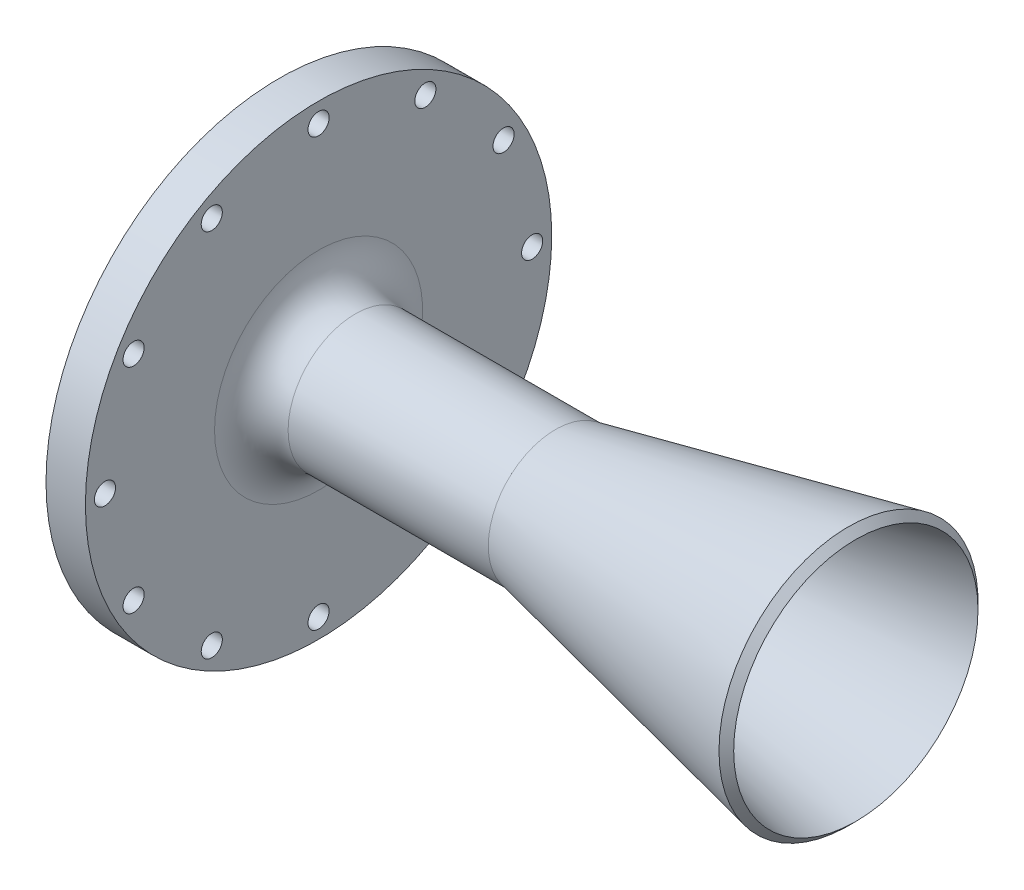
SolidWorks part; units mm, degrees
material "Stainless Steel (ferritic)"
ref_plane "Front Plane" through (0, 0, 0) normal (0, 0, 1) x (1, 0, 0)
ref_plane "Top Plane" through (0, 0, 0) normal (0, 1, 0) x (1, 0, 0)
ref_plane "Right Plane" through (0, 0, 0) normal (1, 0, 0) x (0, 0, -1)
sketch "Sketch2" plane through (0, 0, 0) normal (0, 0, 1) x (1, 0, 0)
  line L0 (0, 0) -> (165.0115, 0) construction
  line L1 (0, 20.5835) -> (0, 56.3562)
  line L2 (0, 56.3562) -> (9.525, 56.3562)
  line L3 (9.525, 56.3562) -> (9.525, 16.256)
  line L11 (66.8065, 16.256) -> (139.7, 31.75)
  line L17 (139.7, 31.75) -> (139.7, 29.5925)
  line L18 (60.325, 12.7208) -> (60.325, 14.351)
  line L19 (60.325, 14.351) -> (10.795, 14.351)
  line L20 (0, 20.5835) -> (10.795, 14.351)
  line L21 (60.325, 12.7208) -> (139.7, 29.5925)
  line L22 (9.525, 16.256) -> (66.8065, 16.256)
  dimension "D2" = 9.525
  dimension "D3" = 1.905
  dimension "D4" = 10.795
  dimension "D5" = 14.351
  dimension "D6" = 31.75
  dimension "D7" = 12
  dimension "D8" = 139.7
  dimension "D9" = 1.6302
  dimension "D10" = 30
  dimension "D11" = 56.3562
  dimension "D12" = 49.53
revolve "Main Structure" add sketch "Sketch2" angle 360 about L0
sketch "Sketch4" plane through (0, 0, 0) normal (-1, 0, 0) x (0, 0, 1)
  circle A0 centre (0, 0) radius 51.6255 construction
  circle A1 centre (0, -51.6255) radius 2.146
  circle A2 centre (-25.8127, -44.709) radius 2.146
  circle A3 centre (-44.709, -25.8128) radius 2.146
  circle A4 centre (-51.6255, 0) radius 2.146
  circle A5 centre (-44.709, 25.8127) radius 2.146
  circle A6 centre (-25.8128, 44.709) radius 2.146
  circle A7 centre (0, 51.6255) radius 2.146
  circle A8 centre (25.8127, 44.709) radius 2.146
  circle A9 centre (44.709, 25.8128) radius 2.146
  circle A10 centre (51.6255, 0) radius 2.146
  circle A11 centre (44.709, -25.8127) radius 2.146
  circle A12 centre (25.8128, -44.709) radius 2.146
  point P29 (0, 0)
  dimension "D1" = 12
  dimension "D2" = 103.251
hole_wizard "Flange Holes" positions "Sketch7" profile "Sketch8" hole size "#7" standard "ANSI Inch" end condition up to next
sketch "Sketch7" plane through (0, 0, 0) normal (-1, 0, 0) x (0, 0, 1)
  point P0 (0, -51.6255)
  point P3 (-25.8127, -44.709)
  point P6 (-44.709, -25.8128)
  point P9 (-51.6255, 0)
  point P12 (-44.709, 25.8127)
  point P15 (-25.8128, 44.709)
  point P18 (0, 51.6255)
  point P21 (25.8127, 44.709)
  point P24 (44.709, 25.8128)
  point P27 (51.6255, 0)
  point P30 (44.709, -25.8127)
  point P33 (25.8128, -44.709)
sketch "Sketch8" plane through (0, -51.6255, 0) normal (0, 1, 0) x (0, 0, 1)
  line L0 (0, 0) -> (0, 9.525)
  line L1 (0, 9.525) -> (2.5527, 9.525)
  line L2 (2.5527, 9.525) -> (2.5527, 0)
  line L5 (2.5527, 0) -> (0, 0)
  line L11 (0, -6.35) -> (0, 107.95) construction
  dimension "Thru Hole Dia." = 5.1054
  dimension "Thru Hole Depth" = 9.525
sketch "Sketch9" plane through (0, 0, 0) normal (-1, 0, 0) x (0, 0, 1)
  line L0 (0, 0) -> (-67.6727, 18.1329) construction
  line L1 (0, 0) -> (-51.6255, 0) construction
  circle A0 centre (0, 0) radius 51.6255 construction
  circle A1 centre (-49.8664, 13.3617) radius 2.9451
  circle A2 centre (49.8664, -13.3617) radius 2.9451
  point P14 (0, 0)
  dimension "D1" = 15
  dimension "D2" = 2
hole_wizard "Dowel Holes" positions "Sketch10" profile "Sketch11" hole size "3/16" standard "ANSI Inch"
sketch "Sketch10" plane through (0, 0, 0) normal (-1, 0, 0) x (0, 0, 1)
  point P0 (49.8664, -13.3617)
  point P3 (-49.8664, 13.3617)
sketch "Sketch11" plane through (0, -13.3617, 49.8664) normal (0, 1, 0) x (0, 0, 1)
  line L0 (0, 0) -> (0, 7.7808)
  line L1 (0, 7.7808) -> (2.3812, 6.35)
  line L2 (2.3812, 6.35) -> (2.3812, 0)
  line L5 (2.3812, 0) -> (0, 0)
  line L10 (0, 7.7808) -> (-2.3812, 6.35) construction
  line L11 (0, -6.35) -> (0, 107.95) construction
  dimension "Hole Dia." = 4.7625
  dimension "Hole Depth" = 6.35
  dimension "Drill Angle" = 118
fillet "Fillet1" radius 8.89 1 edges at (9.525, 0, 16.256)
sketch "Sketch13" plane through (0, 0, 0) normal (0, 1, 0) x (1, 0, 0)
  line L0 (0, 36) -> (3.1496, 0)
  line L1 (0, 56.3562) -> (0, -56.3562) construction
  line L2 (3.1496, 0) -> (0, 0)
  line L3 (0, 0) -> (0, 36)
  dimension "D1" = 36
  dimension "D2" = 5
revolve "Cut-Revolve1" cut sketch "Sketch13" angle 360 about L2
chamfer "Chamfer1" distance 2.54 angle 45 1 edges at (139.7, 0, 31.75) first distance on face at (139.7, 0, 31.75)
sketch "Sketch14" plane through (0, 0, 0) normal (-1, 0, 0) x (0, 0, 1)
  circle A0 centre (0, 0) radius 40.9575
  circle A1 centre (0, 0) radius 46.2915
  dimension "D1" = 81.915
  dimension "D2" = 5.334
extrude "Cut-Extrude1" cut sketch "Sketch14" against normal blind 2.3876
